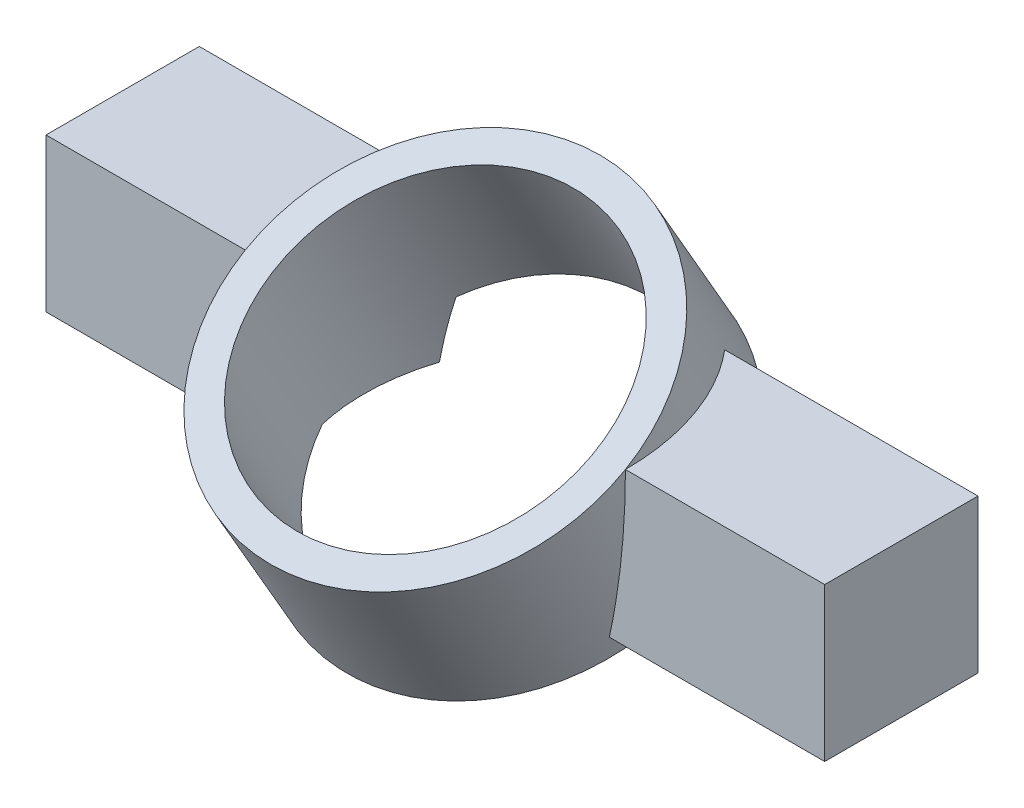
SolidWorks part; units mm, degrees
ref_plane "Front Plane" through (0, 0, 0) normal (0, 0, 1) x (1, 0, 0)
ref_plane "Top Plane" through (0, 0, 0) normal (0, 1, 0) x (1, 0, 0)
ref_plane "Right Plane" through (0, 0, 0) normal (1, 0, 0) x (0, 0, -1)
sketch "Sketch1" plane through (0, 0, 0) normal (0, 1, 0) x (1, 0, 0)
  line L1 (-23.7511, 5) -> (1.6489, 5)
  line L2 (-23.7511, 5) -> (-23.7511, 0)
  line L3 (-23.7511, 0) -> (1.6489, 0)
  line L4 (1.6489, 5) -> (1.6489, 0)
  line L5 (-23.7511, 5) -> (1.6489, 0) construction
  line L6 (-23.7511, 0) -> (1.6489, 5) construction
  point P0 (-11.0511, 2.5)
  dimension "D1" = 5
  dimension "D2" = 25.4
extrude "Boss-Extrude1" add sketch "Sketch1" along normal blind 5
ref_axis "Axis1" through (-23.7511, 5, 0) along (1, 0, 0)
ref_plane "Plane1" through (0, 3.75, 2.1651) normal (0, 0.866, 0.5) x (1, 0, 0)
sketch "Sketch4" plane through (0, 3.75, 2.1651) normal (0, 0.866, 0.5) x (1, 0, 0)
  line L0 (-23.7511, 2.5) -> (1.6489, 2.5) construction
  circle A0 centre (-11.0511, 2.5) radius 5.2
  circle A1 centre (-11.0511, 2.5) radius 6.2
  dimension "D1" = 10.4
  dimension "D2" = 1
extrude "Boss-Extrude2" add sketch "Sketch4" against normal blind 5
sketch "Sketch5" plane through (0, 3.75, 2.1651) normal (0, 0.866, 0.5) x (1, 0, 0)
  line L0 (-11.0511, 7.7) -> (-11.0511, -2.7) construction
  line L2 (-5.8511, 2.5) -> (-16.2511, 2.5) construction
  arc A0 (-5.8511, 2.5) -> (-16.2511, 2.5) centre (-11.0511, 2.5) ccw construction
  arc A1 (-16.2511, 2.5) -> (-5.8511, 2.5) centre (-11.0511, 2.5) ccw construction
  circle A2 centre (-11.0511, 2.5) radius 5.2
  dimension "D1" = 10.4
extrude "Cut-Extrude1" cut sketch "Sketch5" against normal through all
